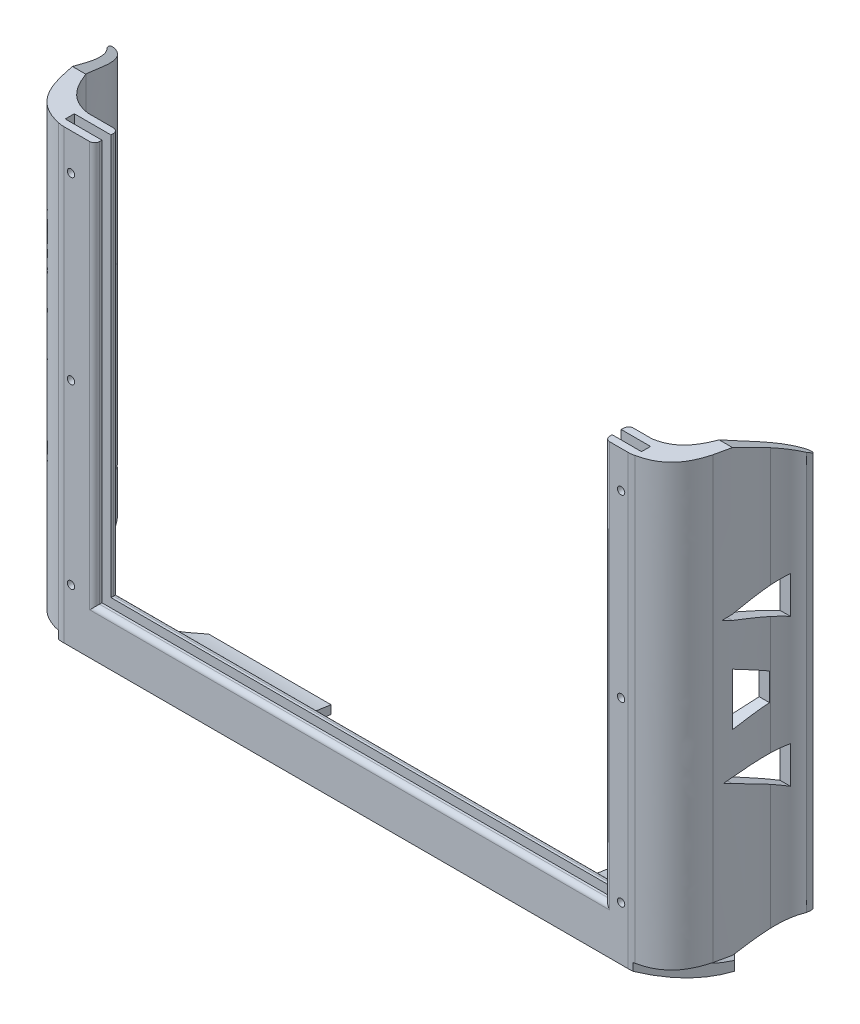
SolidWorks part; units mm, degrees
ref_plane "前视基准面" through (0, 0, 0) normal (0, 0, 1) x (1, 0, 0)
ref_plane "上视基准面" through (0, 0, 0) normal (0, 1, 0) x (1, 0, 0)
ref_plane "右视基准面" through (0, 0, 0) normal (1, 0, 0) x (0, 0, -1)
sketch "草图1" plane through (0, 0, 0) normal (0, 0, 1) x (1, 0, 0)
  line L1 (-117.5, -87.945) -> (117.5, -87.945)
  line L2 (-117.5, -87.945) -> (-117.5, 87.945)
  line L3 (-117.5, 87.945) -> (117.5, 87.945)
  line L4 (117.5, -87.945) -> (117.5, 87.945)
  line L5 (-117.5, -87.945) -> (117.5, 87.945) construction
  line L6 (-117.5, 87.945) -> (117.5, -87.945) construction
  point P0 (0, 0)
  dimension "D1" = 235
  dimension "D2" = 175.89
extrude "凸台-拉伸1" add sketch "草图1" along normal blind 3
sketch "草图2" plane through (0, -87.945, 0) normal (0, -1, 0) x (1, 0, 0)
  line L4 (-117.5, 0) -> (117.5, 0)
  line L5 (117.5, 0) -> (117.5, 3)
  line L6 (117.5, 3) -> (-117.5, 3)
  line L7 (-117.5, 3) -> (-117.5, 0)
  line L8 (-117.5, 0) -> (117.5, 0)
  line L9 (117.5, 0) -> (117.5, 3)
  line L10 (117.5, 3) -> (-117.5, 3)
  line L11 (-117.5, 3) -> (-117.5, 0)
  dimension "D1" = 0
extrude "凸台-拉伸2" add sketch "草图2" along normal blind 4
sketch "草图3" plane through (0, 0, 3) normal (0, 0, 1) x (1, 0, 0)
  line L0 (117.5, -88.945) -> (-117.5, -88.945)
  line L1 (117.5, -91.945) -> (117.5, 87.945) construction
  line L2 (-117.5, 87.945) -> (-117.5, -91.945) construction
  line L3 (-117.5, -88.945) -> (-117.5, -91.945)
  line L4 (-117.5, -91.945) -> (117.5, -91.945)
  line L5 (117.5, -91.945) -> (117.5, -88.945)
  dimension "D1" = 3
extrude "凸台-拉伸3" add sketch "草图3" along normal blind 7
sketch "草图5" plane through (0, 0, 10) normal (0, 0, 1) x (1, 0, 0)
  line L4 (117.5, -91.945) -> (117.5, -88.945)
  line L5 (117.5, -88.945) -> (-117.5, -88.945)
  line L6 (-117.5, -88.945) -> (-117.5, -91.945)
  line L7 (-117.5, -91.945) -> (117.5, -91.945)
  line L8 (117.5, -91.945) -> (117.5, -88.945)
  line L9 (117.5, -88.945) -> (-117.5, -88.945)
  line L10 (-117.5, -88.945) -> (-117.5, -91.945)
  line L11 (-117.5, -91.945) -> (117.5, -91.945)
  dimension "D1" = 0
extrude "切除-拉伸2" cut sketch "草图5" against normal blind 0.3
sketch "草图6" plane through (117.5, 0, 0) normal (1, 0, 0) x (0, 0, -1)
  line L6 (-9.7, -88.945) -> (-9.7, -91.945)
  line L7 (-9.7, -91.945) -> (0, -91.945)
  line L8 (0, -91.945) -> (0, 87.945)
  line L9 (0, 87.945) -> (-3, 87.945)
  line L10 (-3, 87.945) -> (-3, -88.945)
  line L11 (-3, -88.945) -> (-9.7, -88.945)
  line L12 (-9.7, -88.945) -> (-9.7, -91.945)
  line L13 (-9.7, -91.945) -> (0, -91.945)
  line L14 (0, -91.945) -> (0, 87.945)
  line L15 (0, 87.945) -> (-3, 87.945)
  line L16 (-3, 87.945) -> (-3, -88.945)
  line L17 (-3, -88.945) -> (-9.7, -88.945)
  dimension "D1" = 0
extrude "凸台-拉伸4" add sketch "草图6" along normal blind 0.35
sketch "草图7" plane through (-117.5, 0, 0) normal (-1, 0, 0) x (0, 0, 1)
  line L6 (9.7, -91.945) -> (9.7, -88.945)
  line L7 (9.7, -88.945) -> (3, -88.945)
  line L8 (3, -88.945) -> (3, 87.945)
  line L9 (3, 87.945) -> (0, 87.945)
  line L10 (0, 87.945) -> (0, -91.945)
  line L11 (0, -91.945) -> (9.7, -91.945)
  line L12 (9.7, -91.945) -> (9.7, -88.945)
  line L13 (9.7, -88.945) -> (3, -88.945)
  line L14 (3, -88.945) -> (3, 87.945)
  line L15 (3, 87.945) -> (0, 87.945)
  line L16 (0, 87.945) -> (0, -91.945)
  line L17 (0, -91.945) -> (9.7, -91.945)
  dimension "D1" = 0
extrude "凸台-拉伸5" add sketch "草图7" along normal blind 0.35
sketch "草图8" plane through (-117.85, 0, 0) normal (-1, 0, 0) x (0, 0, 1)
  line L0 (0, -91.945) -> (9.7, -91.945)
  line L1 (9.7, -91.945) -> (9.7, 87.945)
  line L2 (9.7, 87.945) -> (0, 87.945)
  line L3 (0, 87.945) -> (0, -91.945)
extrude "凸台-拉伸6" add sketch "草图8" along normal blind 3
sketch "草图9" plane through (117.85, 0, 0) normal (1, 0, 0) x (0, 0, -1)
  line L0 (-9.7, -91.945) -> (0, -91.945)
  line L1 (0, -91.945) -> (0, 87.945)
  line L2 (0, 87.945) -> (-9.7, 87.945)
  line L3 (-9.7, 87.945) -> (-9.7, -91.945)
extrude "凸台-拉伸7" add sketch "草图9" along normal blind 3
sketch "草图10" plane through (-117.85, 0, 0) normal (1, 0, 0) x (0, 0, -1)
  line L0 (-9.7, 87.945) -> (-6.7, 87.945)
  line L1 (-9.7, 87.945) -> (-3, 87.945) construction
  line L2 (-9.7, -88.945) -> (-9.7, 87.945) construction
  line L3 (-9.7, -88.945) -> (-9.7, 87.945)
  line L6 (-6.7, -88.945) -> (-9.7, -88.945)
  line L7 (-6.7, -88.945) -> (-6.7, 87.945)
  dimension "D1" = 3
extrude "凸台-拉伸8" add sketch "草图10" along normal up to surface (235.7 mm away) up to face at (117.85, -0.5, 6.35)
sketch "草图11" plane through (0, 0, 0) normal (0, 0, -1) x (-1, 0, 0)
  line L0 (-105.85, -75.945) -> (102.85, -75.945)
  line L1 (102.85, -75.945) -> (102.85, 87.945)
  line L2 (-120.85, 87.945) -> (120.85, 87.945) construction
  line L3 (-105.85, -75.945) -> (-105.85, 87.945)
  line L4 (120.85, -91.945) -> (-120.85, -91.945) construction
  line L5 (120.85, 87.945) -> (120.85, -91.945) construction
  line L6 (-120.85, -91.945) -> (-120.85, 87.945) construction
  line L7 (-105.85, 87.945) -> (102.85, 87.945)
  dimension "D1" = 16
  dimension "D2" = 18
  dimension "D3" = 15
extrude "切除-拉伸4" cut sketch "草图11" against normal through all
sketch "草图12" plane through (0, 87.945, 0) normal (0, 1, 0) x (1, 0, 0)
  line L0 (120.85, -9.7) -> (149.4239, 34.3)
  line L1 (149.4239, 34.3) -> (149.4239, 44)
  line L2 (149.4239, 44) -> (120.85, 0)
  line L3 (105.85, -9.7) -> (120.85, -9.7) construction
  line L4 (117.85, -3) -> (105.85, -3) construction
  line L11 (120.85, 0) -> (120.85, -9.7)
  line L12 (-120.85, 0) -> (-149.4239, 44)
  line L13 (-149.4239, 44) -> (-149.4239, 34.3)
  line L14 (-149.4239, 34.3) -> (-120.85, -9.7)
  line L15 (-120.85, -9.7) -> (-102.85, -9.7) construction
  line L16 (-102.85, -3) -> (-117.85, -3) construction
  line L17 (-120.85, 0) -> (-120.85, -9.7)
  dimension "D1" = 57
  dimension "D2" = 47
  dimension "D3" = 57
  dimension "D4" = 47
extrude "凸台-拉伸9" add sketch "草图12" against normal up to surface (179.89 mm away) up to face at (0, -91.945, 4.85)
fillet "圆角3" radius 2 3 edges at (105.85, 6, 0) (-102.85, 6, 0) (1.5, -75.945, 0)
fillet "圆角4" radius 2 3 edges at (105.85, 6, 9.7) (-102.85, 6, 9.7) (1.5, -75.945, 9.7)
fillet "圆角5" radius 10 2 edges at (-120.85, -2, 0) (120.85, -2, 0)
sketch "草图13" plane through (0, 0, 9.7) normal (0, 0, 1) x (1, 0, 0)
  line L0 (-112.5, 72.945) -> (-112.5, -72.945) construction
  line L1 (-112.5, -72.945) -> (112.5, -72.945) construction
  line L2 (112.5, -72.945) -> (112.5, 72.945) construction
  line L3 (112.5, 72.945) -> (-112.5, 72.945) construction
  line L4 (120.85, 87.945) -> (120.85, -91.945) construction
  line L6 (-120.85, -91.945) -> (120.85, -91.945) construction
  circle A0 centre (112.5, -0.445) radius 1.5
  circle A1 centre (-112.5, -0.445) radius 1.5
  circle A2 centre (112.5, -72.945) radius 1.5
  circle A3 centre (-112.5, -72.945) radius 1.5
  circle A4 centre (-112.5, 72.945) radius 1.5
  circle A5 centre (112.5, 72.945) radius 1.5
  dimension "D5" = 3
  dimension "D6" = 3
  dimension "D7" = 3
  dimension "D8" = 3
  dimension "D9" = 3
  dimension "D10" = 3
  dimension "D1" = 225
  dimension "D2" = 145.89
  dimension "D3" = 8.35
  dimension "D4" = 19
  dimension "D11" = 72.5
  dimension "D12" = 72.5
extrude "切除-拉伸5" cut sketch "草图13" against normal through all
fillet "圆角6" radius 10 2 edges at (-120.85, -2, 9.7) (120.85, -2, 9.7)
fillet "圆角7" radius 20 2 edges at (149.4239, -2, -34.3) (-149.4239, -2, -34.3)
fillet "圆角8" radius 0.7 2 edges at (149.4239, -2, -44) (-149.4239, -2, -44)
sketch "草图14" plane through (0, -91.945, 0) normal (0, -1, 0) x (1, 0, 0)
  line L0 (123.8071, 5.1464) -> (146.1973, -29.3315) construction
  line L1 (123.8071, 5.1464) -> (146.1973, -29.3315)
  line L2 (-146.1973, -29.3315) -> (-123.8071, 5.1464) construction
  line L3 (-146.1973, -29.3315) -> (-123.8071, 5.1464)
  line L4 (146.1973, -29.3315) -> (126.8071, 5.1464)
  line L5 (126.8071, 5.1464) -> (120.192, 8.4882)
  line L6 (-146.1973, -29.3315) -> (-126.8071, 5.1464)
  line L7 (-126.8071, 5.1464) -> (-120.192, 8.4882)
  line L8 (-126.8071, 5.1464) -> (-123.8071, 5.1464) construction
  line L9 (126.8071, 5.1464) -> (123.8071, 5.1464) construction
  arc A0 (123.8071, 5.1464) -> (115.4204, 9.7) centre (115.4204, -0.3) ccw construction
  arc A1 (-115.4204, 9.7) -> (-123.8071, 5.1464) centre (-115.4204, -0.3) ccw construction
  arc A2 (123.8071, 5.1464) -> (120.192, 8.4882) centre (115.4204, -0.3) ccw
  arc A3 (-120.192, 8.4882) -> (-123.8071, 5.1464) centre (-115.4204, -0.3) ccw
  dimension "D1" = 3
  dimension "D2" = 3
extrude "凸台-拉伸10" add sketch "草图14" against normal up to surface (179.89 mm away) up to face at (121.7311, 87.945, -6.3897)
fillet "圆角9" radius 20 2 edges at (126.8071, -2, 5.1464) (-126.8071, -2, 5.1464)
sketch "草图15" plane through (-117.85, 0, 0) normal (1, 0, 0) x (0, 0, -1)
  line L0 (-6.7, -88.945) -> (-3, -88.945) construction
  line L1 (-9.7, -88.945) -> (-3, -88.945)
  line L3 (-9.6929, -94.945) -> (-9.7, -94.945)
  line L4 (-9.7, 87.945) -> (-9.7, -91.945) construction
  line L5 (-9.7, -88.945) -> (-9.7, -94.945)
  line L6 (42.0181, -91.945) -> (42.0181, 87.945) construction
  line L7 (42.0181, -117.3345) -> (42.0181, 87.945) construction
  line L8 (-7.8902, -91.945) -> (0.1574, -91.945) construction
  line L9 (-7.8902, -91.945) -> (0.1574, -91.945) construction
  line L10 (42.0181, -113.901) -> (42.0181, -117.3345)
  spline S0 degree 2 poles (-3, -88.945) (19.5269, -111.923) (42.0181, -113.901) knots 0 0 0 0.738769 0.738769 0.738769
  spline S1 degree 2 poles (-9.6929, -94.945) (20.0687, -116.0231) (42.0181, -117.3345) knots 0 0 0 0.732583 0.732583 0.732583
  dimension "D1" = 3
extrude "凸台-拉伸12" add sketch "草图15" along normal blind 235
sketch "草图20" plane through (0, -88.945, 0) normal (0, 1, 0) x (1, 0, 0)
  line L2 (-117.85, -9.4004) -> (-117.85, -9.7)
  line L3 (-117.85, -9.7) -> (-115.4204, -9.7)
  line L4 (-117.85, -9.4004) -> (-117.85, -9.7)
  line L5 (-117.85, -9.7) -> (-115.4204, -9.7)
  arc A1 (-117.85, -9.4004) -> (-115.4204, -9.7) centre (-115.4204, 0.3) ccw
  arc A2 (-117.85, -9.4004) -> (-115.4204, -9.7) centre (-115.4204, 0.3) ccw
  dimension "D1" = 0
extrude "切除-拉伸9" cut sketch "草图20" against normal blind 235
sketch "草图21" plane through (0, -88.945, 0) normal (0, 1, 0) x (1, 0, 0)
  line L2 (115.4204, -9.7) -> (117.15, -9.7)
  line L3 (117.15, -9.7) -> (117.15, -9.5493)
  line L4 (115.4204, -9.7) -> (117.15, -9.7)
  line L5 (117.15, -9.7) -> (117.15, -9.5493)
  arc A1 (115.4204, -9.7) -> (117.15, -9.5493) centre (115.4204, 0.3) ccw
  arc A2 (115.4204, -9.7) -> (117.15, -9.5493) centre (115.4204, 0.3) ccw
  dimension "D1" = 0
extrude "切除-拉伸10" cut sketch "草图21" against normal blind 235
sketch "草图22" plane through (0, -88.945, 0) normal (0, 1, 0) x (1, 0, 0)
  line L0 (-57.85, 42.0181) -> (57.15, 42.0181)
  line L1 (117.15, 42.0181) -> (-117.85, 42.0181) construction
  line L2 (57.15, 42.0181) -> (57.15, 17.0181)
  line L3 (57.15, 17.0181) -> (-57.85, 17.0181)
  line L4 (-57.85, 17.0181) -> (-57.85, 42.0181)
  line L5 (117.15, 0.0343) -> (117.15, 42.0181) construction
  line L6 (-117.85, 42.0181) -> (-117.85, 0.0343) construction
  dimension "D1" = 25
  dimension "D2" = 60
  dimension "D3" = 60
extrude "切除-拉伸11" cut sketch "草图22" against normal blind 235
sketch "草图23" plane through (0, 87.945, 0) normal (0, 1, 0) x (1, 0, 0)
  line L0 (115.4204, 0) -> (121.4052, -1.0911)
  line L1 (121.4052, -1.0911) -> (121.4052, -5.5602)
  line L2 (121.4052, -5.5602) -> (117.882, -9.3923)
  arc A0 (115.4204, -9.7) -> (120.192, -8.4882) centre (115.4204, 0.3) ccw construction
  spline S0 degree 3 poles (115.4204, 0) (137.4833, 3.456) (126.1953, 39.0185) (148.9494, 39.7561) knots 0 0 0 0 1 1 1 1
  spline S1 degree 3 poles (117.882, -9.3923) (143.3094, -3.9212) (127.8785, 30.1992) (148.9494, 39.7561) knots 0 0 0 0 1 1 1 1
extrude "凸台-拉伸13" add sketch "草图23" against normal up to surface (179.89 mm away) up to face at (130.9994, -91.945, -11.8803)
sketch "草图24" plane through (0, 87.945, 0) normal (0, 1, 0) x (1, 0, 0)
  line L0 (145.2487, 37.5708) -> (137.7942, 26.0918) construction
  line L1 (145.2487, 37.5708) -> (137.7942, 26.0918)
  line L12 (115.4204, 0) -> (107.85, 0)
  line L13 (105.85, -2) -> (105.85, -3)
  line L14 (105.85, -3) -> (117.85, -3)
  line L15 (117.85, -3) -> (117.85, -6.7)
  line L16 (117.85, -6.7) -> (105.85, -6.7)
  line L17 (105.85, -6.7) -> (105.85, -7.7)
  line L18 (107.85, -9.7) -> (115.4204, -9.7)
  line L19 (133.56, 6.8609) -> (146.1973, 29.3315)
  line L20 (149.4239, 40.2243) -> (149.4239, 41.6368)
  line L21 (148.1369, 42.0181) -> (146.5199, 39.5282)
  line L22 (129.5264, 13.3605) -> (123.8071, 4.5536)
  line L30 (133.56, 6.8609) -> (146.1973, 29.3315)
  line L31 (149.4239, 40.2243) -> (149.4239, 41.6368)
  line L32 (148.1369, 42.0181) -> (146.5199, 39.5282)
  line L33 (129.5264, 13.3605) -> (123.8071, 4.5536)
  arc A6 (122.0966, 2.5549) -> (123.8071, 4.5536) centre (115.4204, 10) ccw
  arc A7 (107.85, 0) -> (105.85, -2) centre (107.85, -2) ccw
  arc A8 (105.85, -7.7) -> (107.85, -9.7) centre (107.85, -7.7) ccw
  arc A9 (115.4204, -9.7) -> (117.882, -9.3923) centre (115.4204, 0.3) ccw
  arc A10 (146.1973, 29.3315) -> (149.4239, 40.2243) centre (129.4239, 40.2243) ccw
  arc A11 (149.4239, 41.6368) -> (148.1369, 42.0181) centre (148.7239, 41.6368) ccw
  arc A12 (122.0966, 2.5549) -> (123.8071, 4.5536) centre (115.4204, 10) ccw
  arc A16 (146.1973, 29.3315) -> (149.4239, 40.2243) centre (129.4239, 40.2243) ccw
  arc A17 (149.4239, 41.6368) -> (148.1369, 42.0181) centre (148.7239, 41.6368) ccw
  spline S0 degree 3 poles (145.2487, 37.5708) (146.3395, 38.3951) (147.5657, 39.1286) (148.9494, 39.7561) knots 0.934334 0.934334 0.934334 0.934334 1 1 1 1
  spline S2 degree 3 poles (133.56, 6.8609) (135.2357, 13.036) (135.8537, 19.9919) (137.7942, 26.0918) knots 0.388916 0.388916 0.388916 0.388916 0.702262 0.702262 0.702262 0.702262
  spline S3 degree 3 poles (122.0966, 2.5549) (125.7432, 5.0551) (127.8947, 8.9798) (129.5264, 13.3605) knots 0.121286 0.121286 0.121286 0.121286 0.364976 0.364976 0.364976 0.364976
  spline S4 degree 3 poles (146.5199, 39.5282) (147.2839, 39.6512) (148.0925, 39.7284) (148.9494, 39.7561) knots 0.962341 0.962341 0.962341 0.962341 1 1 1 1
  spline S5 degree 3 poles (913.8125, -608.3332) (-604.3682, 810.863) (871.5824, -763.835) (-661.472, 629.6078) knots -1.722353 -1.722353 -1.722353 -1.722353 2.743675 2.743675 2.743675 2.743675 only from (122.0966, 2.5549) to (115.4204, 0)
  spline S6 degree 3 poles (-755.1545, 478.2577) (993.1873, -629.8954) (-724.0651, 656.6918) (1030.9974, -434.2643) knots -1.707745 -1.707745 -1.707745 -1.707745 2.768397 2.768397 2.768397 2.768397 only from (117.882, -9.3923) to (133.56, 6.8609)
  spline S7 degree 3 poles (910.7227, -605.4451) (-601.6989, 808.1031) (869.246, -761.5067) (-659.4524, 627.7723) knots -1.719319 -1.719319 -1.719319 -1.719319 2.741712 2.741712 2.741712 2.741712 only from (146.5199, 39.5282) to (129.5264, 13.3605)
  arc M24 (123.8071, 4.5536) -> (122.0966, 2.5549) centre (115.4204, 10) cw
  line M37 (133.56, 6.8609) -> (146.1973, 29.3315)
  arc M38 (146.1973, 29.3315) -> (149.4239, 40.2243) centre (129.4239, 40.2243) ccw
  line M39 (149.4239, 40.2243) -> (149.4239, 41.6368)
  arc M40 (149.4239, 41.6368) -> (148.1369, 42.0181) centre (148.7239, 41.6368) ccw
  line M41 (148.1369, 42.0181) -> (146.5199, 39.5282)
  line M43 (129.5264, 13.3605) -> (123.8071, 4.5536)
  line M45 (145.2487, 37.5708) -> (137.7942, 26.0918)
  dimension "D1" = 0
extrude "切除-拉伸12" cut sketch "草图24" against normal blind 235 contours S4 S0 S2 M41 M45 M37 M38 M39 M40 | S3 M24 M43 region at (141.8905, 87.945, -26.6729) region at (126.2793, 87.945, -7.7579)
sketch "草图25" plane through (0, -88.945, 0) normal (0, 1, 0) x (1, 0, 0)
  line L0 (-0.0004, 0) -> (-0.0004, 34.4782) construction
  arc A0 (-116.2484, 0.0343) -> (-115.4204, 0) centre (-115.4204, 10) ccw construction
  arc A1 (-116.2484, 0.0343) -> (-115.4204, 0) centre (-115.4204, 10) ccw
  dimension "D1" = 115.42
sketch "草图26" plane through (0, 87.945, 0) normal (0, 1, 0) x (1, 0, 0)
  line L3 (121.4052, -5.5602) -> (117.882, -9.3923)
  line L4 (121.4052, -1.0911) -> (121.4052, -5.5602)
  line L5 (115.4204, 0) -> (121.4052, -1.0911)
  line L6 (121.4052, -5.5602) -> (117.882, -9.3923)
  line L7 (121.4052, -1.0911) -> (121.4052, -5.5602)
  line L8 (115.4204, 0) -> (121.4052, -1.0911)
  line L10 (0, -28.6203) -> (0, 28.6203) construction
  line L11 (-115.4204, 0) -> (-121.4052, -1.0911)
  line L12 (-121.4052, -1.0911) -> (-121.4052, -5.5602)
  line L13 (-121.4052, -5.5602) -> (-117.882, -9.3923)
  spline S0 degree 3 poles (-117.882, -9.3923) (-143.3094, -3.9212) (-127.8785, 30.1992) (-148.9494, 39.7561) knots 0 0 0 0 1 1 1 1
  spline S1 degree 3 poles (-148.9494, 39.7561) (-126.1953, 39.0185) (-137.4833, 3.456) (-115.4204, 0) knots 0 0 0 0 1 1 1 1
  spline S2 degree 3 poles (2357.8247, -1988.3899) (-2032.8813, 2258.0925) (2305.7983, -2206.388) (-2122.7757, 1995.0149) knots -2.677671 -2.677671 -2.677671 -2.677671 3.701735 3.701735 3.701735 3.701735 only from (148.9494, 39.7561) to (115.4204, 0)
  spline S3 degree 3 poles (-2430.0359, 1570.984) (2655.4641, -1798.7685) (-2388.5282, 1821.4129) (2712.4634, -1514.3959) knots -2.669133 -2.669133 -2.669133 -2.669133 3.730339 3.730339 3.730339 3.730339 only from (117.882, -9.3923) to (148.9494, 39.7561)
  spline S4 degree 3 poles (148.9494, 39.7561) (126.1953, 39.0185) (137.4833, 3.456) (115.4204, 0) knots 0 0 0 0 1 1 1 1
  spline S5 degree 3 poles (117.882, -9.3923) (143.3094, -3.9212) (127.8785, 30.1992) (148.9494, 39.7561) knots 0 0 0 0 1 1 1 1
  dimension "D1" = 0
extrude "凸台-拉伸14" add sketch "草图26" against normal up to surface (179.89 mm away) up to face at (-131.1254, -91.945, -11.8983)
sketch "草图27" plane through (0, 87.945, 0) normal (0, 1, 0) x (1, 0, 0)
  line L0 (-137.7942, 26.0918) -> (-145.2487, 37.5708) construction
  line L1 (-137.7942, 26.0918) -> (-145.2487, 37.5708)
  line L11 (-115.4204, -9.7) -> (-104.85, -9.7)
  line L12 (-102.85, -7.7) -> (-102.85, -6.7)
  line L13 (-102.85, -6.7) -> (-117.85, -6.7)
  line L14 (-117.85, -6.7) -> (-117.85, -3)
  line L15 (-117.85, -3) -> (-102.85, -3)
  line L16 (-102.85, -3) -> (-102.85, -2)
  line L17 (-104.85, 0) -> (-115.4204, 0)
  line L18 (-123.8071, 4.5536) -> (-129.5264, 13.3605)
  line L19 (-146.5199, 39.5282) -> (-148.1369, 42.0181)
  line L20 (-149.4239, 41.6368) -> (-149.4239, 40.2243)
  line L21 (-146.1973, 29.3315) -> (-133.56, 6.8609)
  line L29 (-123.8071, 4.5536) -> (-129.5264, 13.3605)
  line L30 (-146.5199, 39.5282) -> (-148.1369, 42.0181)
  line L31 (-149.4239, 41.6368) -> (-149.4239, 40.2243)
  line L32 (-146.1973, 29.3315) -> (-133.56, 6.8609)
  arc A6 (-117.882, -9.3923) -> (-115.4204, -9.7) centre (-115.4204, 0.3) ccw
  arc A7 (-104.85, -9.7) -> (-102.85, -7.7) centre (-104.85, -7.7) ccw
  arc A8 (-102.85, -2) -> (-104.85, 0) centre (-104.85, -2) ccw
  arc A9 (-123.8071, 4.5536) -> (-122.0966, 2.5549) centre (-115.4204, 10) ccw
  arc A10 (-148.1369, 42.0181) -> (-149.4239, 41.6368) centre (-148.7239, 41.6368) ccw
  arc A11 (-149.4239, 40.2243) -> (-146.1973, 29.3315) centre (-129.4239, 40.2243) ccw
  arc A15 (-123.8071, 4.5536) -> (-122.0966, 2.5549) centre (-115.4204, 10) ccw
  arc A16 (-148.1369, 42.0181) -> (-149.4239, 41.6368) centre (-148.7239, 41.6368) ccw
  arc A17 (-149.4239, 40.2243) -> (-146.1973, 29.3315) centre (-129.4239, 40.2243) ccw
  spline S0 degree 3 poles (-145.2487, 37.5708) (-146.3395, 38.3951) (-147.5657, 39.1286) (-148.9494, 39.7561) knots 0.934334 0.934334 0.934334 0.934334 1 1 1 1
  spline S3 degree 3 poles (-1031.0005, -434.2663) (724.0648, 656.6919) (-993.1839, -629.8927) (755.1476, 478.2533) knots -1.7684 -1.7684 -1.7684 -1.7684 2.707739 2.707739 2.707739 2.707739 only from (-133.56, 6.8609) to (-117.882, -9.3923)
  spline S4 degree 3 poles (661.4838, 629.6185) (-871.5871, -763.8404) (604.3665, 810.8607) (-913.8039, -608.3251) knots -1.743686 -1.743686 -1.743686 -1.743686 2.722345 2.722345 2.722345 2.722345 only from (-115.4204, 0) to (-122.0966, 2.5549)
  spline S5 degree 3 poles (659.4531, 627.7729) (-869.2419, -761.503) (601.6903, 808.0938) (-910.7091, -605.4324) knots -1.741713 -1.741713 -1.741713 -1.741713 2.719306 2.719306 2.719306 2.719306 only from (-129.5264, 13.3605) to (-146.5199, 39.5282)
  spline S6 degree 3 poles (-133.56, 6.8609) (-135.2357, 13.036) (-135.8537, 19.9919) (-137.7942, 26.0918) knots 0.388916 0.388916 0.388916 0.388916 0.702262 0.702262 0.702262 0.702262
  spline S9 degree 3 poles (-148.9494, 39.7561) (-148.0925, 39.7284) (-147.2839, 39.6512) (-146.5199, 39.5282) knots 0 0 0 0 0.037659 0.037659 0.037659 0.037659
  spline S10 degree 3 poles (-129.5264, 13.3605) (-127.8947, 8.9798) (-125.7432, 5.0551) (-122.0966, 2.5549) knots 0.635024 0.635024 0.635024 0.635024 0.878714 0.878714 0.878714 0.878714
  dimension "D1" = 0
extrude "切除-拉伸13" cut sketch "草图27" against normal blind 235
sketch "草图28" plane through (0, -88.945, 0) normal (0, 1, 0) x (1, 0, 0)
  line L0 (-57.85, 17.0181) -> (-72.0646, 42.0181)
  line L1 (-57.85, 42.0181) -> (-117.85, 42.0181) construction
  line L2 (-72.0646, 42.0181) -> (-87.6768, 11.2914)
  line L3 (-87.6768, 11.2914) -> (-105.1475, 42.0181)
  line L4 (-105.1475, 42.0181) -> (-117.85, 17.0181)
  line L5 (-117.85, 42.0181) -> (-117.85, 0.0343) construction
  line L7 (57.15, 42.0181) -> (57.15, 17.0181) construction
  line L13 (57.15, 42.0181) -> (57.15, 17.0181)
  line L17 (-117.85, 42.0181) -> (-117.85, 17.0181)
  line L18 (-57.85, 42.0181) -> (-117.85, 42.0181)
  line L19 (-57.85, 17.0181) -> (-57.85, 42.0181) construction
  line L21 (-57.85, 17.0181) -> (-57.85, 42.0181)
  line L24 (-57.85, 17.0181) -> (-117.85, 17.0181)
  line L25 (-105.1475, 42.0181) -> (-94.1848, 17.0181)
  line L26 (-72.0646, 42.0181) -> (-82.006, 17.0181)
  line L27 (0, -28.4449) -> (0, 28.4449) construction
  line L28 (72.0646, 42.0181) -> (82.006, 17.0181)
  line L29 (105.1475, 42.0181) -> (94.1848, 17.0181)
  line L30 (57.85, 17.0181) -> (117.85, 17.0181)
  line L31 (57.85, 42.0181) -> (57.15, 42.0181)
  line L32 (57.85, 42.0181) -> (117.85, 42.0181)
  line L33 (117.85, 42.0181) -> (117.85, 17.0181)
  line L34 (105.1475, 42.0181) -> (117.85, 17.0181)
  line L35 (87.6768, 11.2914) -> (105.1475, 42.0181)
  line L36 (72.0646, 42.0181) -> (87.6768, 11.2914)
  line L37 (57.85, 17.0181) -> (72.0646, 42.0181)
  line L38 (57.85, 17.0181) -> (57.15, 17.0181)
  line L39 (-49.7833, 17.0181) -> (-46.5333, 8.2739)
  line L40 (57.15, 17.0181) -> (-57.85, 17.0181) construction
  line L41 (-46.5333, 8.2739) -> (-43.2833, 17.0181)
  line L42 (-43.2833, 17.0181) -> (-49.7833, 17.0181)
  line L43 (-39.2833, 17.0181) -> (-36.0333, 8.2739)
  line L44 (-36.0333, 8.2739) -> (-32.7833, 17.0181)
  line L45 (-32.7833, 17.0181) -> (-39.2833, 17.0181)
  line L46 (-28.7833, 17.0181) -> (-25.5333, 8.2739)
  line L47 (-25.5333, 8.2739) -> (-22.2833, 17.0181)
  line L48 (-22.2833, 17.0181) -> (-28.7833, 17.0181)
  line L49 (-18.2833, 17.0181) -> (-15.0333, 8.2739)
  line L50 (-15.0333, 8.2739) -> (-11.7833, 17.0181)
  line L51 (-11.7833, 17.0181) -> (-18.2833, 17.0181)
  line L52 (-7.7833, 17.0181) -> (-4.5333, 8.2739)
  line L53 (-4.5333, 8.2739) -> (-1.2833, 17.0181)
  line L54 (-1.2833, 17.0181) -> (-7.7833, 17.0181)
  line L55 (2.7167, 17.0181) -> (5.9667, 8.2739)
  line L56 (5.9667, 8.2739) -> (9.2167, 17.0181)
  line L57 (9.2167, 17.0181) -> (2.7167, 17.0181)
  line L58 (13.2167, 17.0181) -> (16.4667, 8.2739)
  line L59 (16.4667, 8.2739) -> (19.7167, 17.0181)
  line L60 (19.7167, 17.0181) -> (13.2167, 17.0181)
  line L61 (23.7167, 17.0181) -> (26.9667, 8.2739)
  line L62 (26.9667, 8.2739) -> (30.2167, 17.0181)
  line L63 (30.2167, 17.0181) -> (23.7167, 17.0181)
  line L64 (34.2167, 17.0181) -> (37.4667, 8.2739)
  line L65 (37.4667, 8.2739) -> (40.7167, 17.0181)
  line L66 (40.7167, 17.0181) -> (34.2167, 17.0181)
  line L67 (44.7167, 17.0181) -> (47.9667, 8.2739)
  line L68 (47.9667, 8.2739) -> (51.2167, 17.0181)
  line L69 (51.2167, 17.0181) -> (44.7167, 17.0181)
  line L70 (77.0114, 32.2821) -> (99.6118, 32.2821)
  line L71 (-77.0114, 32.2821) -> (-99.6118, 32.2821)
  dimension "D2" = 6.5
  dimension "D1" = 10
extrude "切除-拉伸14" cut sketch "草图28" against normal blind 235 contours L41 L42 L39 | L44 L45 L43 | L47 L48 L46 | L50 L51 L49 | L53 L54 L52 | L56 L57 L55 | L59 L60 L58 | L62 L63 L61 | L68 L69 L67 | L2 L71 L3 L24 | L2 L24 L3 | L70 L36 L30 L35 | L30 L36 L35 | L65 L66 L64 region at (-88.1248, -88.945, -26.1035) region at (-87.7923, -88.945, -15.1092) region at (88.1248, -88.945, -26.1035) region at (87.7923, -88.945, -15.1092) region at (-46.5333, -88.945, -14.1033) region at (-36.0333, -88.945, -14.1033) region at (-25.5333, -88.945, -14.1033) region at (-15.0333, -88.945, -14.1033) region at (-4.5333, -88.945, -14.1033) region at (5.9667, -88.945, -14.1033) region at (16.4667, -88.945, -14.1033) region at (26.9667, -88.945, -14.1033) region at (47.9667, -88.945, -14.1033)
sketch "草图29" plane through (117.85, 0, 0) normal (-1, 0, 0) x (0, 0, 1)
  line L0 (-39.5282, -91.945) -> (-13.3605, -91.945) construction
  line L1 (-39.5282, -91.945) -> (-13.3605, -91.945) construction
  line L2 (-13.3605, 87.945) -> (-39.5282, 87.945) construction
  line L3 (-13.3605, 87.945) -> (-39.5282, 87.945) construction
  line L4 (-39.5282, -91.945) -> (-39.5282, 87.945)
  line L5 (-13.3605, 87.945) -> (-13.3605, 67.2701) construction
  line L6 (-13.3605, -91.945) -> (-39.5282, -82.4318)
  line L7 (-39.5282, -82.4318) -> (-13.3605, -72.9186)
  line L8 (-13.3605, 87.945) -> (-39.5282, 77.6075)
  line L9 (-39.5282, 77.6075) -> (-13.3605, 67.2701)
  line L10 (-13.3605, -51.4353) -> (-39.5282, -41.7915)
  line L11 (-39.5282, -41.7915) -> (-13.3605, -31.146)
  line L12 (-13.3605, -12.0033) -> (-39.5282, -2.1306)
  line L13 (-39.5282, -2.1306) -> (-13.3605, 9.4318)
  line L14 (-13.3605, 28.9183) -> (-39.5282, 39.9228)
  line L15 (-39.5282, 39.9228) -> (-13.3605, 50.9273)
  line L16 (-39.5282, 87.945) -> (-39.5282, -91.945) construction
  line L17 (-39.5282, 87.945) -> (-39.5282, -91.945) construction
  line L21 (-13.3605, 53.0228) -> (-13.3605, 65.0787)
  line L22 (-13.3605, -91.945) -> (-57.8855, -105.6069)
  line L23 (-57.8855, -105.6069) -> (-67.2683, 29.573)
  line L24 (-67.2683, 29.573) -> (-57.8855, 136.889)
  line L25 (-57.8855, 136.889) -> (-13.3605, 107.4823)
  line L26 (-13.3605, 107.4823) -> (-13.3605, 87.945)
  line L27 (-39.5282, -62.3116) -> (-13.3605, -70.713)
  line L28 (-39.5282, -62.3116) -> (-13.3605, -53.8553)
  line L29 (-39.5282, -21.3287) -> (-13.3605, -28.825)
  line L30 (-39.5282, -21.3287) -> (-13.3605, -14.2828)
  line L31 (-39.5282, 19.3677) -> (-13.3605, 11.7566)
  line L32 (-39.5282, 19.3677) -> (-13.3605, 26.7073)
  line L33 (-39.5282, 58.7543) -> (-13.3605, 53.0228)
  line L34 (-39.5282, 58.7543) -> (-13.3605, 65.0787)
  line L35 (-13.3605, -72.9186) -> (-10.2481, -71.6903)
  line L36 (-10.2481, -71.6903) -> (-13.3605, -70.713)
  line L37 (-13.3605, -53.8553) -> (-10.2481, -52.5461)
  line L38 (-10.2481, -52.5461) -> (-13.3605, -51.4353)
  line L39 (-13.3605, -31.146) -> (-10.2481, -29.8368)
  line L40 (-10.2481, -29.8368) -> (-13.3605, -28.825)
  line L41 (-13.3605, -14.2828) -> (-10.2232, -13.0892)
  line L42 (-10.2232, -13.0892) -> (-13.3605, -12.0033)
  line L43 (-13.3605, 9.4318) -> (-10.2237, 10.6253)
  line L44 (-10.2237, 10.6253) -> (-13.3605, 11.7566)
  line L45 (-13.3605, 26.7073) -> (-9.6919, 28.1031)
  line L46 (-9.6919, 28.1031) -> (-13.3605, 28.9183)
  line L47 (-13.3605, 50.9273) -> (-10.263, 52.1058)
  line L48 (-10.263, 52.1058) -> (-13.3605, 53.0228)
  line L49 (-13.3605, 65.0787) -> (-10.3167, 66.2367)
  line L50 (-10.3167, 66.2367) -> (-13.3605, 67.2701)
  line L51 (-13.3605, -72.9186) -> (-13.3605, -91.945) construction
  line L52 (-31.8313, 80.6482) -> (-31.8313, -85.23)
  line L53 (-13.3605, -31.146) -> (-13.3605, -51.4353) construction
  line L54 (-25.8141, 3.9291) -> (-25.8141, -7.3048)
  line L55 (-13.3605, 9.4318) -> (-13.3605, -12.0033)
  line L57 (-13.3605, 50.9273) -> (-13.3605, 28.9183) construction
  line L58 (-13.3605, 65.0787) -> (-13.3605, 53.0228) construction
extrude "切除-拉伸18" cut sketch "草图29" against normal through all and the other way through all contours L26 L25 L24 L23 L22 L6 L4 L8 | L14 L52 L32 L45 L46 | L29 L52 L11 L39 L40 | L55 L13 L54 L12 region at (117.85, 22.8671, -47.5641) region at (117.85, -30.6609, -24.5805) region at (117.85, 28.6027, -24.5762) region at (117.85, -1.4659, -18.9391)
sketch "草图31" plane through (0, -91.945, 0) normal (0, -1, 0) x (1, 0, 0)
  line L0 (-145.5399, -42.1524) -> (-143.3518, -32.8533)
  line L1 (-143.3518, -32.8533) -> (-155.9067, -42.8259)
  line L2 (-155.9067, -42.8259) -> (-145.5399, -42.1524)
  line L3 (145.1873, -42.6706) -> (142.6747, -31.8224)
  line L4 (142.6747, -31.8224) -> (155.1316, -41.7353)
  line L5 (155.1316, -41.7353) -> (145.1873, -42.6706)
  line L6 (-139.6766, -40.4279) -> (-145.3025, -34.4028)
  line L7 (-139.6766, -40.4279) -> (-145.5399, -42.1524)
  line L8 (137.7236, -41.2309) -> (146.4407, -32.0315)
  line L9 (145.1873, -42.6706) -> (137.7236, -41.2309)
  spline S0 degree 2 poles (-141.9361, -38.0081) (-145.5937, -39.3705) (-143.6318, -36.192) knots 0 0 0 1 1 1
  spline S1 degree 3 poles (-146.5199, -39.5282) (-134.402, -37.5774) (-133.5261, -24.099) (-129.5264, -13.3605) knots 0.037659 0.037659 0.037659 0.037659 0.635024 0.635024 0.635024 0.635024 construction
  spline S2 degree 3 poles (-137.7942, -26.0918) (-139.2313, -30.6094) (-141.3939, -34.6575) (-145.2487, -37.5708) knots 0.702262 0.702262 0.702262 0.702262 0.934334 0.934334 0.934334 0.934334 construction
  spline S3 degree 2 poles (143.0513, -35.6085) (145.0248, -38.9564) (141.1916, -37.571) knots 0 0 0 1 1 1
  spline S4 degree 3 poles (145.2487, -37.5708) (141.3939, -34.6575) (139.2313, -30.6094) (137.7942, -26.0918) knots 0.065666 0.065666 0.065666 0.065666 0.297738 0.297738 0.297738 0.297738 construction
  spline S5 degree 3 poles (129.5264, -13.3605) (133.5261, -24.099) (134.402, -37.5774) (146.5199, -39.5282) knots 0.364976 0.364976 0.364976 0.364976 0.962341 0.962341 0.962341 0.962341 construction
extrude "切除-拉伸19" cut sketch "草图31" against normal through all contours L8 S3 L9 L3 | L6 S0 L0 L7 | L5 L3 L4 | L1 L2 L0 region at (-143.03, -91.945, -39.8372) region at (142.0376, -91.945, -40.0751)
chamfer "倒角1" distance 10 angle 45 2 edges at (-117.85, -115.6177, -42.0181) (117.15, -115.6177, -42.0181)
ref_plane "基准面1" through (143.0513, 79.156, -35.6085) normal (0, -1, 0) x (-1, 0, 0)
